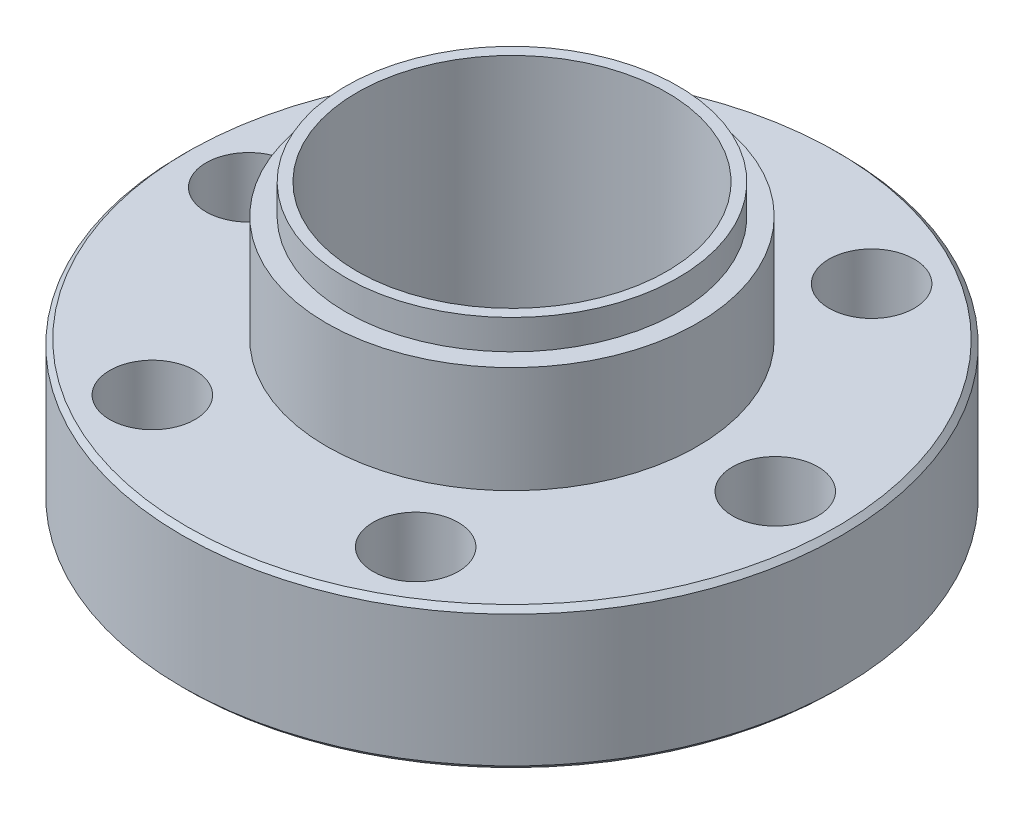
SolidWorks part; units mm, degrees
ref_plane "Front Plane" through (0, 0, 0) normal (0, 0, 1) x (1, 0, 0)
ref_plane "Top Plane" through (0, 0, 0) normal (0, 1, 0) x (1, 0, 0)
ref_plane "Right Plane" through (0, 0, 0) normal (1, 0, 0) x (0, 0, -1)
ref_plane "Plane1" through (0, 0, 0) normal (0, 0, -1) x (-1, 0, 0)
sketch "Sketch1" plane through (0, 0, 0) normal (0, 0, -1) x (-1, 0, 0)
  line L0 (-9.144, 1.2954) -> (0, 1.2954)
  line L1 (0, 1.2954) -> (0, 7.239)
  line L2 (0, 7.239) -> (-16.637, 7.239)
  line L3 (-16.637, 7.239) -> (-16.891, 6.985)
  line L4 (-16.891, 6.985) -> (-16.891, 0)
  line L5 (-16.891, 0) -> (-10.7188, 0)
  line L6 (-10.7188, 0) -> (-10.7188, 1.2336)
  line L7 (-10.7188, 1.2336) -> (-9.144, 0.6604)
  line L8 (-9.144, 0.6604) -> (-9.144, 1.2954)
  line L9 (0, 0) -> (0, 7.239) construction
revolve "Revolve1" add sketch "Sketch1" angle 360 about L9 reverse direction yes
sketch "Sketch2" plane through (0, 7.239, 0) normal (0, 1, 0) x (-1, 0, 0)
  circle A0 centre (0, 0) radius 9.4996
extrude "Boss-Extrude1" add sketch "Sketch2" along normal blind 5.461
sketch "Sketch3" plane through (0, 12.7, 0) normal (0, 1, 0) x (-1, 0, 0)
  circle A0 centre (0, 0) radius 8.509
extrude "Boss-Extrude2" add sketch "Sketch3" along normal blind 1.524
hole_wizard "M13 Clearance Hole1" positions "Sketch5" profile "Sketch4" hole size "M13" standard "ANSI Metric"
sketch "Sketch5" plane through (0, 14.224, 0) normal (0, 1, 0) x (1, 0, 0)
  point P0 (0, 0)
sketch "Sketch4" plane through (0, 14.224, 0) normal (1, 0, 0) x (0, 0, 1)
  line L0 (0, 0) -> (0, 12.9286)
  line L1 (0, 12.9286) -> (7.9375, 12.9286)
  line L2 (7.9375, 12.9286) -> (7.9375, 0)
  line L5 (7.9375, 0) -> (0, 0)
  line L10 (0, 12.9286) -> (-7.9375, 12.9286) construction
  line L11 (0, -6.35) -> (0, 107.95) construction
  dimension "Hole Dia." = 15.875
  dimension "Hole Depth" = 12.9286
  dimension "Drill Angle" = 180
hole_wizard "M4 Clearance Hole1" positions "Sketch7" profile "Sketch6" hole size "M4" standard "ANSI Metric"
sketch "Sketch7" plane through (0, 0, 0) normal (0, -1, 0) x (-1, 0, 0)
  point P0 (-13.4874, 0)
  point P1 (-6.7437, -11.6804)
  point P2 (6.7437, -11.6804)
  point P3 (13.4874, 0)
  point P4 (6.7437, 11.6804)
  point P5 (-6.7437, 11.6804)
sketch "Sketch6" plane through (13.4874, 0, 0) normal (1, 0, 0) x (0, 0, -1)
  line L0 (0, 0) -> (0, 14.224)
  line L1 (0, 14.224) -> (2.1844, 14.224)
  line L2 (2.1844, 14.224) -> (2.1844, 0)
  line L5 (2.1844, 0) -> (0, 0)
  line L11 (0, -6.35) -> (0, 107.95) construction
  dimension "Thru Hole Dia." = 4.3688
  dimension "Thru Hole Depth" = 14.224
chamfer "Chamfer1" distance 0.254 angle 45 1 edges at (0, 0, 16.891)
ref_point "Point1"
ref_point "Point2"
ref_axis "Axis1" through (6.7437, 0, -11.6804) along (-0.5, 0, 0.866)
ref_axis "Axis2" through (0, 1.2954, 0) along (0, 1, 0)
